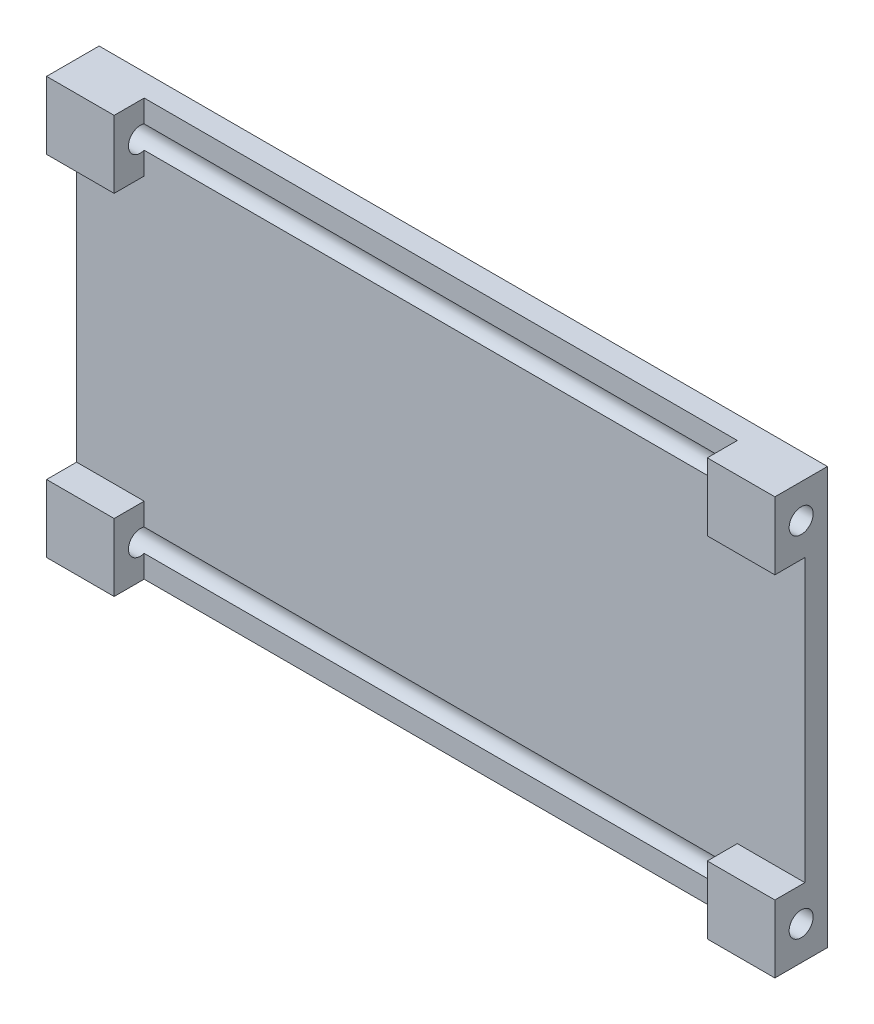
SolidWorks part; units mm, degrees
ref_plane "Alzado" through (0, 0, 0) normal (0, 0, 1) x (1, 0, 0)
ref_plane "Planta" through (0, 0, 0) normal (0, 1, 0) x (1, 0, 0)
ref_plane "Vista lateral" through (0, 0, 0) normal (1, 0, 0) x (0, 0, -1)
sketch "Croquis1" plane through (0, 0, 0) normal (0, 0, 1) x (1, 0, 0)
  line L1 (-48.5, 27.75) -> (48.5, 27.75)
  line L2 (-48.5, 27.75) -> (-48.5, -27.75)
  line L3 (-48.5, -27.75) -> (48.5, -27.75)
  line L4 (48.5, 27.75) -> (48.5, -27.75)
  line L5 (-48.5, 27.75) -> (48.5, -27.75) construction
  line L6 (-48.5, -27.75) -> (48.5, 27.75) construction
  point P0 (0, 0)
  dimension "D1" = 97
  dimension "D2" = 55.5
extrude "Saliente-Extruir1" add sketch "Croquis1" against normal blind 3
sketch "Croquis2" plane through (0, 0, 0) normal (0, 0, 1) x (1, 0, 0)
  line L0 (0, 27.75) -> (0, -27.75) construction
  line L1 (-48.5, 27.75) -> (-39.5, 27.75)
  line L2 (-48.5, 27.75) -> (-48.5, 18.75)
  line L3 (-48.5, 18.75) -> (-39.5, 18.75)
  line L4 (-39.5, 27.75) -> (-39.5, 18.75)
  line L5 (48.5, 27.75) -> (-48.5, 27.75) construction
  line L6 (-48.5, -27.75) -> (48.5, -27.75) construction
  line L7 (-48.5, 0) -> (48.5, 0) construction
  line L8 (-48.5, 27.75) -> (-48.5, -27.75) construction
  line L9 (48.5, -27.75) -> (48.5, 27.75) construction
  line L10 (-48.5, -18.75) -> (-39.5, -18.75)
  line L11 (-39.5, -27.75) -> (-39.5, -18.75)
  line L12 (-48.5, -27.75) -> (-39.5, -27.75)
  line L13 (-48.5, -27.75) -> (-48.5, -18.75)
  line L14 (48.5, -27.75) -> (48.5, -18.75)
  line L15 (48.5, -27.75) -> (39.5, -27.75)
  line L16 (39.5, -27.75) -> (39.5, -18.75)
  line L17 (48.5, -18.75) -> (39.5, -18.75)
  line L18 (48.5, 18.75) -> (39.5, 18.75)
  line L19 (39.5, 27.75) -> (39.5, 18.75)
  line L20 (48.5, 27.75) -> (39.5, 27.75)
  line L21 (48.5, 27.75) -> (48.5, 18.75)
  dimension "D1" = 9
  dimension "D2" = 9
extrude "Saliente-Extruir2" add sketch "Croquis2" along normal blind 4
sketch "Croquis3" plane through (-48.5, 0, 0) normal (-1, 0, 0) x (0, 0, 1)
  line L0 (4, 23.25) -> (-3, 23.25) construction
  line L1 (4, 27.75) -> (4, 18.75) construction
  line L2 (-3, 27.75) -> (-3, -27.75) construction
  line L3 (0, 0) -> (-3, 0) construction
  circle A0 centre (0.5, 23.25) radius 1.6
  circle A1 centre (0.5, -23.25) radius 1.6
  dimension "D1" = 3.2
extrude "Cortar-Extruir1" cut sketch "Croquis3" against normal through all
